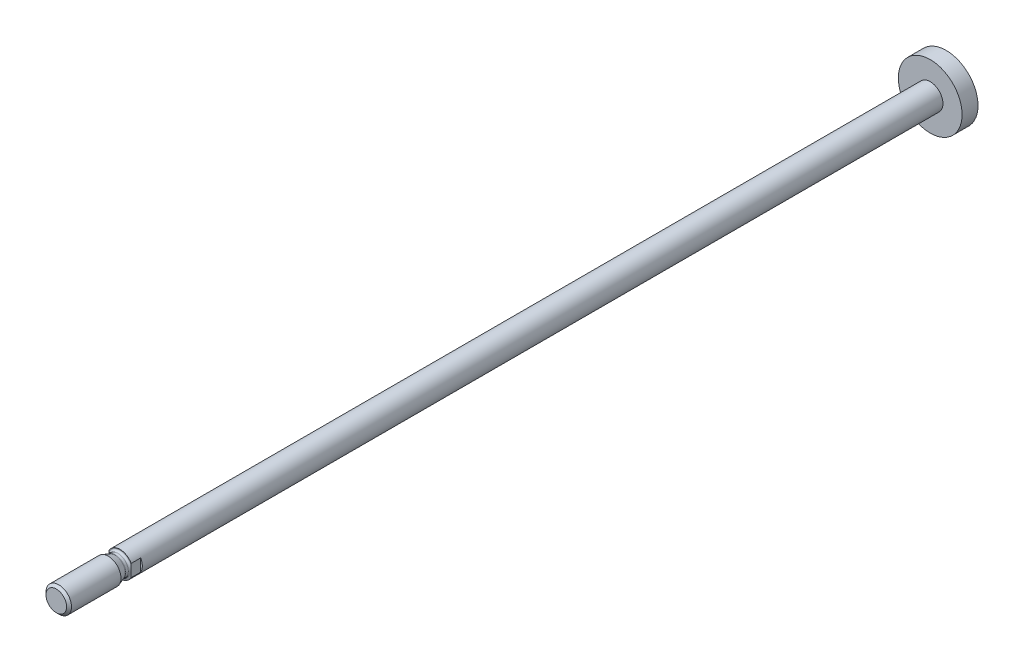
SolidWorks part; units mm, degrees
ref_plane "Ebene vorne" through (0, 0, 0) normal (0, 0, 1) x (1, 0, 0)
ref_plane "Ebene oben" through (0, 0, 0) normal (0, 1, 0) x (1, 0, 0)
ref_plane "Ebene rechts" through (0, 0, 0) normal (1, 0, 0) x (0, 0, -1)
sketch "Skizze1" plane through (0, 0, 0) normal (1, 0, 0) x (0, 0, -1)
  line L0 (-4, 0) -> (-4, 4)
  line L1 (-4, 4) -> (250.3, 4)
  line L2 (250.3, 4) -> (250.3, 10)
  line L3 (250.3, 10) -> (255.3, 10)
  line L4 (255.3, 10) -> (255.3, 0)
  line L5 (255.3, 0) -> (-4, 0)
  line L6 (255.3, 0) -> (-4, 0) construction
revolve "Rotation1" add sketch "Skizze1" angle 360 about L6 reverse direction yes
sketch "Skizze2" plane through (0, 0, 0) normal (1, 0, 0) x (0, 0, -1)
  line L0 (-24, 0) -> (-24, 3.233)
  line L1 (-24, 3.233) -> (-23.233, 4)
  line L2 (-23.233, 4) -> (-7.698, 4)
  line L3 (-7.698, 4) -> (-5.5994, 3.2362)
  line L4 (-5.3942, 3.2) -> (-4.6, 3.2)
  line L5 (-4, 3.8) -> (-4, 4)
  line L6 (-4, 4) -> (-3, 4)
  line L7 (-3, 4) -> (-3, 0)
  line L8 (-3, 0) -> (-24, 0)
  line L9 (-3, 0) -> (-24, 0) construction
  arc A0 (-5.5994, 3.2362) -> (-5.3942, 3.2) centre (-5.3942, 3.8) ccw
  arc A1 (-4.6, 3.2) -> (-4, 3.8) centre (-4.6, 3.8) ccw
revolve "Rotation2" add sketch "Skizze2" angle 360 about L9 reverse direction yes
cosmetic thread "Gewindedarstellung1" parameters "D1"=16.302, "D2"=6.466
ref_plane "Ebene1" through (0, 0, 4) normal (0, 0, 1) x (1, 0, 0)
ref_plane "Ebene2" through (0, 0, 1) normal (0, 0, 1) x (1, 0, 0)
sketch "Skizze3" plane through (0, 0, 1) normal (0, 0, 1) x (1, 0, 0)
  line L0 (-7, 14) -> (-7, -7)
  line L1 (-7, -7) -> (-3.5, -7)
  line L2 (-3.5, -7) -> (-3.5, 7)
  line L3 (-3.5, 7) -> (3.5, 7)
  line L4 (3.5, 7) -> (3.5, -7)
  line L5 (3.5, -7) -> (7, -7)
  line L6 (7, -7) -> (7, 14)
  line L7 (7, 14) -> (-7, 14)
extrude "Schnitt-Linear austragen1" cut sketch "Skizze3" along normal blind 4
ref_plane "Ebene3" through (0, 0, -512) normal (0, 0, 1) x (1, 0, 0)
ref_plane "Ebene4" through (0, 0, 20) normal (0, 0, 1) x (1, 0, 0)
ref_plane "Ebene5" through (0, 0, 12) normal (0, 0, 1) x (1, 0, 0)
ref_plane "FDT_KSAUFSATZ XY" through (0, 0, 12) normal (0, 0, 1) x (1, 0, 0)
ref_plane "FDT_KSAUFSATZ XZ" through (0, 0, 0) normal (0, 1, 0) x (1, 0, 0)
ref_plane "FDT_KSAUFSATZ YZ" through (0, 0, 0) normal (-1, 0, 0) x (0, 0, 1)
ref_axis "FDT_KSAUFSATZ X" through (80.9, 0, 12) along (-1, 0, 0)
ref_axis "FDT_KSAUFSATZ Y" through (0, 50, 12) along (0, -1, 0)
ref_axis "FDT_KSAUFSATZ Z" through (0, 0, 80.9) along (0, 0, -1)
sketch3d "FDT_KSAUFSATZ"
  point P0 (0, 0, 12)
ref_plane "FDT_NUT XY" through (0, 0, 12) normal (0, 0, 1) x (1, 0, 0)
ref_plane "FDT_NUT XZ" through (0, 0, 0) normal (0, 1, 0) x (1, 0, 0)
ref_plane "FDT_NUT YZ" through (0, 0, 0) normal (-1, 0, 0) x (0, 0, 1)
ref_axis "FDT_NUT X" through (80.9, 0, 12) along (-1, 0, 0)
ref_axis "FDT_NUT Y" through (0, 50, 12) along (0, -1, 0)
ref_axis "FDT_NUT Z" through (0, 0, 80.9) along (0, 0, -1)
sketch3d "FDT_NUT"
  point P0 (0, 0, 12)
ref_plane "KS XY" through (0, 0, 0) normal (0, 0, -1) x (-1, 0, 0)
ref_plane "KS XZ" through (0, 0, 0) normal (0, 1, 0) x (1, 0, 0)
ref_plane "KS YZ" through (0, 0, 0) normal (1, 0, 0) x (0, 0, -1)
ref_axis "KS X" through (-80.9, 0, 0) along (1, 0, 0)
ref_axis "KS Y" through (0, 50, 0) along (0, -1, 0)
ref_axis "KS Z" through (0, 0, -80.9) along (0, 0, 1)
sketch3d "KS"
  point P0 (0, 0, 0)
ref_plane "NUT1 XY" through (0, 0, 20) normal (0, 0, 1) x (1, 0, 0)
ref_plane "NUT1 XZ" through (0, 0, 0) normal (0, -1, 0) x (-1, 0, 0)
ref_plane "NUT1 YZ" through (0, 0, 0) normal (1, 0, 0) x (0, 0, -1)
ref_axis "NUT1 X" through (-80.9, 0, 20) along (1, 0, 0)
ref_axis "NUT1 Y" through (0, -50, 20) along (0, 1, 0)
ref_axis "NUT1 Z" through (0, 0, 80.9) along (0, 0, -1)
sketch3d "NUT1"
  point P0 (0, 0, 20)
